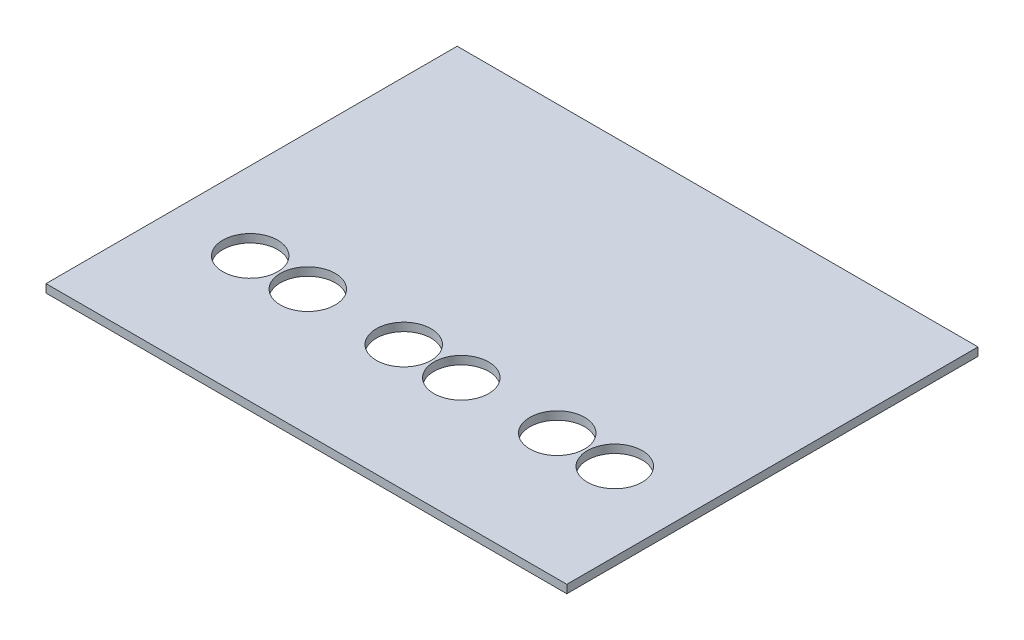
SolidWorks part; units mm, degrees
ref_plane "Front Plane" through (0, 0, 0) normal (0, 0, 1) x (1, 0, 0)
ref_plane "Top Plane" through (0, 0, 0) normal (0, 1, 0) x (1, 0, 0)
ref_plane "Right Plane" through (0, 0, 0) normal (1, 0, 0) x (0, 0, -1)
sketch "Sketch1" plane through (0, 0, 0) normal (0, 1, 0) x (1, 0, 0)
  line L1 (0, 0) -> (190, 0)
  line L2 (0, 0) -> (0, 150)
  line L3 (0, 150) -> (190, 150)
  line L4 (190, 0) -> (190, 150)
  circle A0 centre (28.5, 46) radius 10
  circle A1 centre (49.5, 46) radius 10
  circle A2 centre (84.5, 46) radius 10
  circle A3 centre (105.5, 46) radius 10
  circle A4 centre (140.5, 46) radius 10
  circle A5 centre (161.5, 46) radius 10
  dimension "D3" = 46
  dimension "D1" = 190
  dimension "D2" = 150
  dimension "D4" = 46
  dimension "D5" = 46
  dimension "D6" = 46
  dimension "D7" = 46
  dimension "D8" = 46
  dimension "D9" = 21
  dimension "D10" = 21
  dimension "D11" = 21
  dimension "D12" = 77
  dimension "D13" = 77
  dimension "D14" = 28.5
sheet metal parameters "Sheet-Metal1" thickness 3 parameters "D1"=0.7366
base flange "Base-Flange1" sketch "Sketch1" thickness 3 reverse thickness direction no parameters "D1"=0.7366
flat pattern "Flat-Pattern1" [suppressed]
sketch "Bend-Lines1" plane through (0, 0, 0) normal (0, 1, 0) x (1, 0, 0)
sketch3d "Bounding-Box1" [suppressed]
  line L0 (-190, 150, 0) -> (0, 150, 0) construction
  line L1 (-190, 0, 0) -> (0, 0, 0) construction
  line L2 (-190, 150, 0) -> (-190, 0, 0) construction
  line L3 (0, 150, 0) -> (0, 0, 0) construction
